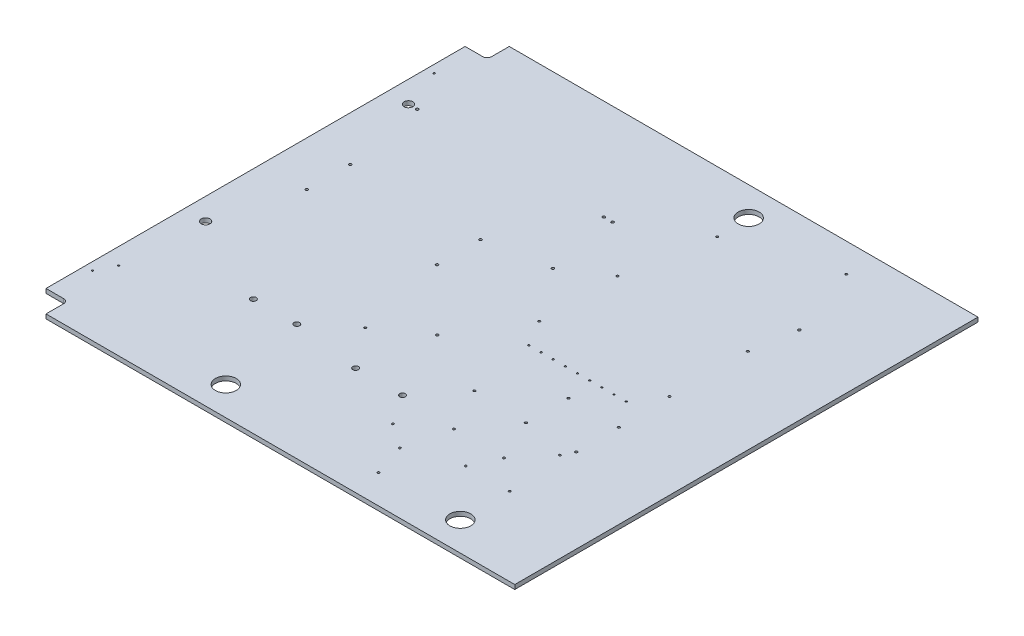
SolidWorks part; units mm, degrees
ref_plane "Front Plane" through (0, 0, 0) normal (0, 0, 1) x (1, 0, 0)
ref_plane "Top Plane" through (0, 0, 0) normal (0, 1, 0) x (1, 0, 0)
ref_plane "Right Plane" through (0, 0, 0) normal (1, 0, 0) x (0, 0, -1)
sketch "Sketch1" plane through (0, 0, 0) normal (1, 0, 0) x (0, 0, -1)
  line L0 (0, 0) -> (-533.4, 0)
  line L1 (-533.4, 0) -> (-533.4, 5)
  line L2 (-533.4, 5) -> (0, 5)
  line L6 (0, 5) -> (0, 0)
  dimension "D1" = 533.4
extrude "Boss-Extrude1" add sketch "Sketch1" along normal blind 565.15
sketch "BotthomHoles-Sketch2" plane through (0, 5, 0) normal (0, 1, 0) x (1, 0, 0)
  line L1 (565.15, 0) -> (565.15, -533.4) construction
  line L2 (565.15, -533.4) -> (0, -533.4) construction
  line L3 (565.15, 0) -> (0, 0) construction
  line L4 (0, 0) -> (0, -533.4) construction
  circle A0 centre (334.275, -33.175) radius 12
  circle A25 centre (199.275, -500.225) radius 12
  circle A26 centre (469.275, -500.225) radius 12
  dimension "D10" = 24
  dimension "D2" = 95.875
  dimension "D3" = 270
  dimension "D4" = 135
  dimension "D5" = 33.175
  dimension "D6" = 33.175
  dimension "D8" = 500.225
  dimension "D7" = 199.275
  dimension "D9" = 334.275
  dimension "D11" = 469.275
extrude "BottomStepperHoles-Cut-Extrude1" cut sketch "BotthomHoles-Sketch2" against normal through all
sketch "BottomPSUHolesSketch2" plane through (0, 5, 0) normal (0, 1, 0) x (1, 0, 0)
  line L0 (0, 0) -> (0, -533.4) construction
  line L1 (565.15, -533.4) -> (0, -533.4) construction
  line L2 (565.15, 0) -> (0, 0) construction
  circle A0 centre (201.5, -209.2) radius 1.5
  circle A1 centre (201.5, -259.2) radius 1.5
  circle A2 centre (51.5, -209.2) radius 1.5
  circle A3 centre (51.5, -259.2) radius 1.5
  circle A6 centre (180, -399.2) radius 3.25
  circle A7 centre (130, -399.2) radius 3.25
  circle A8 centre (257.75, -409.2) radius 3.25
  circle A9 centre (311.75, -409.2) radius 3.25
  dimension "D4" = 6.5
  dimension "D3" = 51.5
  dimension "D1" = 150
  dimension "D2" = 50
  dimension "D7" = 209.2
  dimension "D5" = 50
  dimension "D8" = 140
  dimension "D10" = 134.2
  dimension "D11" = 274.2
  dimension "D12" = 324.2
  dimension "D13" = 201.5
  dimension "D14" = 54
  dimension "D15" = 77.75
  dimension "D16" = 10
  dimension "D9" = 78.5
  dimension "D17" = 130
  dimension "D18" = 124.2
  dimension "D19" = 257.75
  dimension "D20" = 311.75
extrude "BottomPSUHolesCut-Extrude1" cut sketch "BottomPSUHolesSketch2" against normal through all
sketch "OctopusHolesSketch2" plane through (0, 5, 0) normal (0, 1, 0) x (1, 0, 0)
  line L0 (0, 0) -> (0, -533.4) construction
  line L1 (565.15, -533.4) -> (0, -533.4) construction
  circle A0 centre (316.75, -256.7) radius 1.35
  circle A1 centre (466.75, -256.7) radius 1.35
  circle A2 centre (316.75, -166.7) radius 1.35
  circle A3 centre (466.75, -166.7) radius 1.35
  dimension "D1" = 150
  dimension "D3" = 2.7
  dimension "D2" = 90
  dimension "D4" = 115.25
  dimension "D5" = 42.5
  dimension "D6" = 316.75
  dimension "D7" = 466.75
  dimension "D8" = 276.7
  dimension "D9" = 366.7
extrude "OctopusMountHolesCut-Extrude1" cut sketch "OctopusHolesSketch2" against normal through all
sketch "PowrCableGuideMountHolesSketch2" plane through (0, 5, 0) normal (0, 1, 0) x (1, 0, 0)
  line L0 (0, 0) -> (0, -533.4) construction
  line L1 (565.15, -533.4) -> (0, -533.4) construction
  circle A0 centre (271.75, -329.2) radius 1.5
  circle A1 centre (271.75, -196.2) radius 1.5
  dimension "D2" = 3
  dimension "D1" = 133
  dimension "D3" = 45
  dimension "D5" = 271.75
  dimension "D6" = 337.2
  dimension "D7" = 204.2
  dimension "D4" = 29.5
extrude "PowerCableGuideMountHolesCut-Extrude1" cut sketch "PowrCableGuideMountHolesSketch2" against normal through all
sketch "RPIHolesSketch2" plane through (0, 5, 0) normal (0, 1, 0) x (1, 0, 0)
  line L0 (0, 0) -> (0, -533.4) construction
  line L1 (565.15, -533.4) -> (0, -533.4) construction
  circle A4 centre (468.25, -316.7) radius 1.35
  circle A5 centre (468.25, -365.7) radius 1.35
  circle A6 centre (410.25, -316.7) radius 1.35
  circle A7 centre (410.25, -365.7) radius 1.35
  point P4 (282.575, -533.4)
  dimension "D7" = 2.7
  dimension "D1" = 58
  dimension "D2" = 49
  dimension "D3" = 60
  dimension "D4" = 1.5
  dimension "D5" = 410.25
  dimension "D6" = 468.25
  dimension "D8" = 167.7
  dimension "D9" = 216.7
extrude "RPIMountHolesCut-Extrude1" cut sketch "RPIHolesSketch2" against normal through all
sketch "CableHolesSketch2" plane through (0, 5, 0) normal (0, 1, 0) x (1, 0, 0)
  line L3 (565.15, -533.4) -> (0, -533.4) construction
  line L9 (0, 0) -> (0, -533.4) construction
  line L12 (565.15, 0) -> (0, 0) construction
  circle A10 centre (25, -115.65) radius 5
  circle A11 centre (260, -115.65) radius 1.5
  circle A12 centre (25, -349.2) radius 5
  circle A13 centre (9, -463.4) radius 1
  circle A14 centre (9, -70) radius 1
  circle A16 centre (19, -443.4) radius 1
  circle A17 centre (475, -115.65) radius 1.5
  circle A18 centre (250, -115.65) radius 1.5
  circle A19 centre (35, -115.65) radius 1.5
  dimension "D6" = 50
  dimension "D5" = 215
  dimension "D2" = 10
  dimension "D7" = 2
  dimension "D17" = 3
  dimension "D1" = 70
  dimension "D3" = 70
  dimension "D4" = 10
  dimension "D8" = 9
  dimension "D9" = 20
  dimension "D10" = 25
  dimension "D11" = 417.75
  dimension "D12" = 90
  dimension "D13" = 184.2
  dimension "D14" = 463.4
  dimension "D15" = 260
  dimension "D16" = 8.25
  dimension "D18" = 475
  dimension "D19" = 215
  dimension "D20" = 10
  dimension "D21" = 10
  dimension "D22" = 35
  dimension "D23" = 250
extrude "CableHolesCut-Extrude1" cut sketch "CableHolesSketch2" against normal through all
sketch "Sketch2" plane through (0, 5, 0) normal (0, 1, 0) x (1, 0, 0)
  line L0 (565.15, -533.4) -> (0, -533.4) construction
  line L1 (0, 0) -> (0, -533.4) construction
  circle A0 centre (334.75, -286.7) radius 1
  circle A1 centre (348.75, -286.7) radius 1
  circle A2 centre (362.75, -286.7) radius 1
  circle A3 centre (376.75, -286.7) radius 1
  circle A4 centre (390.75, -286.7) radius 1
  circle A5 centre (404.75, -286.7) radius 1
  circle A6 centre (418.75, -286.7) radius 1
  circle A7 centre (432.75, -286.7) radius 1
  circle A8 centre (446.75, -286.7) radius 1
  dimension "D10" = 14
  dimension "D11" = 2
  dimension "D1" = 18
  dimension "D2" = 14
  dimension "D3" = 14
  dimension "D4" = 14
  dimension "D5" = 14
  dimension "D6" = 14
  dimension "D7" = 14
  dimension "D8" = 14
  dimension "D9" = 30
  dimension "D12" = 246.7
  dimension "D13" = 334.75
extrude "OctopusRouting holesCut-Extrude1" cut sketch "Sketch2" against normal through all
sketch "Sketch3" plane through (0, 5, 0) normal (0, 1, 0) x (1, 0, 0)
  line L0 (565.15, -533.4) -> (0, -533.4) construction
  line L1 (0, 0) -> (0, -533.4) construction
  circle A0 centre (469.275, -443.4) radius 1.25
  circle A1 centre (418.75, -443.4) radius 1.25
  circle A2 centre (432.75, -413.4) radius 1.25
  circle A3 centre (375, -413.4) radius 1.25
  circle A4 centre (375, -500.225) radius 1.25
  circle A5 centre (362.75, -463.4) radius 1.25
  circle A6 centre (334.75, -443.4) radius 1.25
  circle A7 centre (446.75, -33.175) radius 1.25
  circle A8 centre (334.75, -70) radius 1.25
  circle A9 centre (348.75, -363.4) radius 1.25
  circle A10 centre (223, -363.4) radius 1.25
  circle A11 centre (462, -378.4) radius 1.25
  dimension "D3" = 2.5
  dimension "D1" = 90
  dimension "D2" = 469.275
  dimension "D4" = 418.75
  dimension "D5" = 120
  dimension "D6" = 432.75
  dimension "D7" = 375
  dimension "D8" = 33.175
  dimension "D9" = 70
  dimension "D10" = 362.75
  dimension "D11" = 334.75
  dimension "D12" = 500.225
  dimension "D13" = 446.75
  dimension "D14" = 463.4
  dimension "D15" = 334.75
  dimension "D16" = 170
  dimension "D17" = 348.75
  dimension "D18" = 223
  dimension "D19" = 462
  dimension "D20" = 155
extrude "CornerClampHoleCuts-Extrude1" cut sketch "Sketch3" against normal through all
sketch "CornerCableKnotchesSketch4" plane through (0, 5, 0) normal (0, 1, 0) x (1, 0, 0)
  line L0 (0, -25.4) -> (20.4, -25.4)
  line L1 (25.4, 0) -> (25.4, -20.4)
  line L2 (565.15, 0) -> (0, 0) construction
  line L3 (0, -25.4) -> (0, 0)
  line L4 (0, 0) -> (0, -533.4) construction
  line L5 (0, 0) -> (25.4, 0)
  line L6 (0, -508) -> (20.4, -508)
  line L7 (25.4, -513) -> (25.4, -533.4)
  line L8 (565.15, -533.4) -> (0, -533.4) construction
  line L9 (0, -508) -> (0, -533.4)
  line L10 (0, -533.4) -> (25.4, -533.4)
  arc A0 (20.4, -25.4) -> (25.4, -20.4) centre (20.4, -20.4) ccw
  arc A1 (25.4, -513) -> (20.4, -508) centre (20.4, -513) ccw
  circle A2 centre (25, -115.65) radius 5 construction
  dimension "D1" = 25.4
extrude "CornerCableKnotchCut-Extrude1" cut sketch "CornerCableKnotchesSketch4" against normal through all
equation "\"RailThickness\"= .125in'Spec"
equation "\"Nema17MountStepperHoleDiameter\"= 24mm'Spec"
equation "\"SideRailLength\"= 21.75in"
equation "\"D10@BotthomHoles-Sketch2\" = \"Nema17MountStepperHoleDiameter\""
equation "\"D1@Boss-Extrude1\"=\"LowerEnclosureLength\""
equation "\"BedLength\"= \"BuildPlateLength\""
equation "\"DistanceBetweenFrontToBackStepperHoles\"= \"BedLength\" - \"BuildPlateStandoffHolesDistanceFromFrontOrBackSide\" * 2'Equals 270"
equation "\"LowerEnclosureThickness\"= 5mm"
equation "\"FrontOrBackRailLength\"= 20.5in"
equation "\"D1@Sketch1\"=\"LowerEncloseWidth\""
equation "\"D2@Sketch1\"=\"LowerEnclosureThickness\""
equation "\"24VPSUMountingHolesShortDistanceBetween\"= 50mm'Yours may differ"
equation "\"24VPSUMountingHolesLongDistanceBetween\"= 150mm'Yours may differ"
equation "\"24VPSUMountingHoleOffsetFromEitherSide\"= 32.5mm'Yours may differ"
equation "\"24VPSUMountingHoleDiameter\"= 3mm'Yours may differ"
equation "\"D6@BottomPSUHolesSketch2\" = \"24VPSUMountingHoleDiameter\""
equation "\"RPi4BoardMountingHoleDiameter\"= 2.7mm'Spec"
equation "\"OctopusV1.1BoardMountingHoleOffsetFromAllEdges\"= 5mm'Spec"
equation "\"OctopusV1.1BoardMountingHoleLengthDistanceBetween\"= 150mm'Spec"
equation "\"OctopusV1.1BoardMountingHoleWidthDistanceBetween\"= 90mm'Spec"
equation "\"D7@RPIHolesSketch2\" = \"RPi4BoardMountingHoleDiameter\""
equation "\"RPi4BoardMountingHoleLengthDistanceBetween\"= 58mm'Spec"
equation "\"OctopusV1.1BoardMountingHoleDiameter\"= 2.7mm'Spec"
equation "\"CWD4890MountingHoleWidthDistance\"= 50mm'Spec"
equation "\"24VPSULength\"= 213mm'Spec"
equation "\"D3@OctopusHolesSketch2\"=\"OctopusV1.1BoardMountingHoleDiameter\""
equation "\"24VPSUMountingHoleOffsetFromFront\"= 32.5mm"
equation "\"DistanceBetween24VPSUAndOctopus\"= \"24VPSUMountingHoleOffsetFromFront\" + \"OctopusV1.1BoardMountingHoleOffsetFromAllEdges\" + 77.75'77.75mm gives 10mm before and after 60mm cable guide"
equation "\"GapBetweenVerticalSupportsAndRails\"= \"RailThickness\" * 2"
equation "\"LowerEncloseWidth\"= \"FrontOrBackRailLength\" + \"GapBetweenVerticalSupportsAndRails\" * 2"
equation "\"Nema17MountStepperHoleFromBack\"= 30mm"
equation "\"D2@BotthomHoles-Sketch2\"=\"DistanceFromFrontSideToFirstLeftStepperHoleMountYSValue\" + \"Nema17StepperMountSlotDistance\"/2 + \"GapBetweenVerticalSupportsAndRails\""
equation "\"D3@BotthomHoles-Sketch2\"=\"DistanceBetweenFrontToBackStepperHoles\""
equation "\"D4@BotthomHoles-Sketch2\"=\"DistanceBetweenFrontToBackStepperHoles\"/2"
equation "\"D5@BotthomHoles-Sketch2\"=\"Nema17MountStepperHoleFromBack\" + \"RailThickness\""
equation "\"D6@BotthomHoles-Sketch2\"=\"Nema17MountStepperHoleFromBack\" + \"RailThickness\""
equation "\"LowerEnclosureLength\"= \"SideRailLength\" + \"GapBetweenVerticalSupportsAndRails\" * 2"
equation "\"DistanceFromFrontSideToFirstLeftStepperHoleMountYSValue\"= 74.025mm"
equation "\"BuildPlateStandoffHolesDistanceFromFrontOrBackSide\"= 41mm"
equation "\"BuildPlateLength\"= 352mm'Spec"
equation "\"D1@BottomPSUHolesSketch2\"=\"24VPSUMountingHolesLongDistanceBetween\""
equation "\"D2@BottomPSUHolesSketch2\"=\"24VPSUMountingHolesShortDistanceBetween\""
equation "\"24VPSUOffsetFromBack\"= ( \"24VPSULength\" - \"24VPSUMountingHolesLongDistanceBetween\" ) / 2 + 20mm"
equation "\"24VPSUOffsetFromRightSide\"= ( \"LowerEncloseWidth\" - \"24VPSUWidth\" ) / 2"
equation "\"24VPSUWidth\"= 115mm'Yours may differ"
equation "\"D3@BottomPSUHolesSketch2\"=\"24VPSUOffsetFromBack\""
equation "\"D1@OctopusHolesSketch2\"=\"OctopusV1.1BoardMountingHoleLengthDistanceBetween\""
equation "\"D2@OctopusHolesSketch2\"=\"OctopusV1.1BoardMountingHoleWidthDistanceBetween\""
equation "\"D4@OctopusHolesSketch2\" = \"DistanceBetween24VPSUAndOctopus\""
equation "\"RPI4BoardMountingHoleWidthDistanceBetween\"= 49mm"
equation "\"D7@BottomPSUHolesSketch2\"=\"24VPSUOffsetFromRightSide\""
equation "\"D1@RPIHolesSketch2\"=\"RPi4BoardMountingHoleLengthDistanceBetween\""
equation "\"D2@RPIHolesSketch2\"=\"RPI4BoardMountingHoleWidthDistanceBetween\""
equation "\"D5@BottomPSUHolesSketch2\"=\"CWD4890MountingHoleWidthDistance\""
equation "\"OctopusV1.1ToPSUNegTerminalOffset\"= \"24VPSUNegTerminalOffsetFromSide\" - \"24VPSUMountingHoleOffsetFromEitherSide\" + \"OctopusV1.1NegTerminalOffsetFromSide\" + \"OctopusV1.1BoardMountingHoleOffsetFromAllEdges\""
equation "\"24VPSUNegTerminalOffsetFromSide\"= 50.5mm"
equation "\"OctopusV1.1NegTerminalOffsetFromSide\"= 19.5mm"
equation "\"D5@OctopusHolesSketch2\" = \"OctopusV1.1ToPSUNegTerminalOffset\""
equation "\"PowerCableGuideMountingHoleDistanceBetweenValue\"=133"
equation "\"D1@PowrCableGuideMountHolesSketch2\" = \"PowerCableGuideMountingHoleDistanceBetweenValue\""
equation "\"D2@PowrCableGuideMountHolesSketch2\" = \"24VPSUMountingHoleDiameter\""
equation "\"RCNUNMountingHoleWidthDistance\"= 54mm"
equation "\"D14@BottomPSUHolesSketch2\"=\"RCNUNMountingHoleWidthDistance\""
equation "\"OctopusToPowerCableGuideOffset\"= 29.5mm'This asligned perfectly"
equation "\"D4@PowrCableGuideMountHolesSketch2\"=\"OctopusToPowerCableGuideOffset\""
equation "\"VSWidth\"= 1.25in'Spec"
equation "\"D1@CornerCableKnotchesSketch4\" = \"VSWidth\" - \"RailThickness\" * 2"
equation "\"Nema17StepperMountSlotDistance\"= 31mm'Spec"
